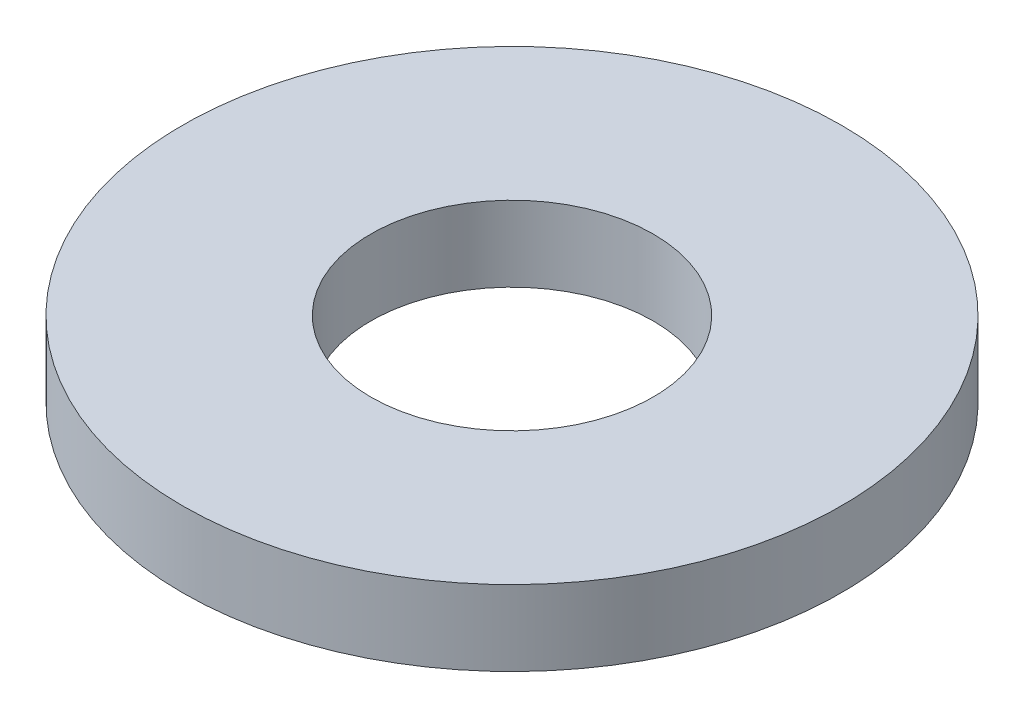
SolidWorks part; units mm, degrees
ref_plane "Front Plane" through (0, 0, 0) normal (0, 0, 1) x (1, 0, 0)
ref_plane "Top Plane" through (0, 0, 0) normal (0, 1, 0) x (1, 0, 0)
ref_plane "Right Plane" through (0, 0, 0) normal (1, 0, 0) x (0, 0, -1)
sketch "Sketch1" plane through (0, 0, 0) normal (0, 1, 0) x (1, 0, 0)
  circle A0 centre (0, 0) radius 70
  dimension "FLANGE_OD" = 140
extrude "Boss-Extrude1" add sketch "Sketch1" along normal blind 16
sketch "Sketch2" plane through (0, 0, 0) normal (0, 1, 0) x (1, 0, 0)
  circle A0 centre (0, 0) radius 30
  dimension "BORE_D" = 60
extrude "Cut-Extrude1" cut sketch "Sketch2" along normal through all
sketch "Sketch3" plane through (0, 16, 0) normal (0, 1, 0) x (1, 0, 0)
  circle A0 centre (0, 0) radius 18.3404 construction
  circle A1 centre (-18.3404, 0) radius 2.6642
  dimension "BOLT_D" = 5.3283
  dimension "BOLT_PCD" = 36.6808
extrude "Cut-Extrude2" cut sketch "Sketch3" against normal blind 12.0891 rebuild error yes
pattern_circular "CirPattern1" count 5 over 360 rebuild error yes
